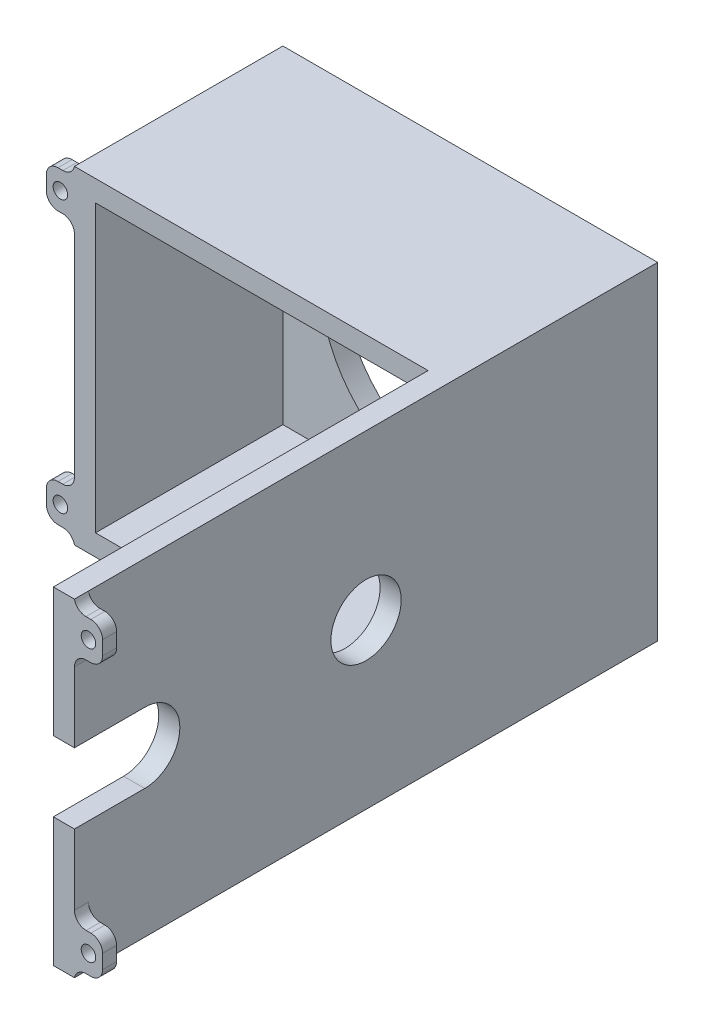
SolidWorks part; units mm, degrees
ref_plane "Front Plane" through (0, 0, 0) normal (1, 0, 0) x (0, 1, 0)
ref_plane "Top Plane" through (0, 0, 0) normal (0, 0, 1) x (0, 1, 0)
ref_plane "Right Plane" through (0, 0, 0) normal (0, 1, 0) x (-1, 0, 0)
sketch "Sketch1" plane through (0, 0, 0) normal (0, 0, 1) x (0, 1, 0)
  line L1 (-35, -40) -> (35, -40)
  line L2 (-35, -40) -> (-35, 40)
  line L3 (-35, 40) -> (35, 40)
  line L4 (35, -40) -> (35, 40)
  line L5 (-35, -40) -> (35, 40) construction
  line L6 (-35, 40) -> (35, -40) construction
  point P0 (0, 0)
  dimension "D1" = 70
  dimension "D2" = 80
extrude "Boss-Extrude1" add sketch "Sketch1" along normal blind 4.5
sketch "Sketch2" plane through (0, 0, 4.5) normal (0, 0, 1) x (1, 0, 0)
  line L0 (40, 35) -> (-40, 35) construction
  line L1 (40, -35) -> (35.5, -35)
  line L2 (40, -35) -> (40, 35)
  line L3 (40, 35) -> (35.5, 35)
  line L4 (35.5, -35) -> (35.5, 35)
  dimension "D1" = 4.5
extrude "Boss-Extrude2" add sketch "Sketch2" along normal blind 120
sketch "Sketch3" plane through (0, 0, 4.5) normal (0, 0, 1) x (1, 0, 0)
  line L0 (35.5, 35) -> (-40, 35)
  line L1 (-40, 35) -> (-40, -35)
  line L2 (-40, -35) -> (35.5, -35)
  line L3 (35.5, -35) -> (35.5, -30.5)
  line L4 (35.5, 35) -> (35.5, -35) construction
  line L5 (35.5, -30.5) -> (-35.5, -30.5)
  line L6 (-35.5, -30.5) -> (-35.5, 30.5)
  line L7 (-35.5, 30.5) -> (35.5, 30.5)
  line L8 (35.5, 30.5) -> (35.5, 35)
  dimension "D1" = 4.5
  dimension "D2" = 4.5
extrude "Boss-Extrude3" add sketch "Sketch3" along normal blind 40
sketch "Sketch4" plane through (0, 0, 0) normal (0, 0, -1) x (1, 0, 0)
  circle A0 centre (0, 0) radius 27.5
  dimension "D1" = 55
extrude "Cut-Extrude1" cut sketch "Sketch4" against normal up to next
sketch "Sketch5" plane through (35.5, 0, 0) normal (-1, 0, 0) x (0, -1, 0)
  line L0 (0, 124.5) -> (0, 0) construction
  line L1 (-35, 124.5) -> (35, 124.5) construction
  line L3 (-7.5, 124.5) -> (7.5, 124.5)
  line L4 (7.5, 124.5) -> (7.5, 109.5)
  line L5 (-7.5, 109.5) -> (-7.5, 124.5)
  line L6 (-35, 0) -> (35, 0) construction
  arc A0 (7.5, 109.5) -> (-7.5, 109.5) centre (0, 109.5) cw
  circle A1 centre (0, 62.25) radius 7.5
  dimension "D2" = 15
  dimension "D3" = 15
  dimension "D1" = 15
extrude "Cut-Extrude2" cut sketch "Sketch5" against normal up to next
sketch "Sketch6" plane through (0, 0, 124.5) normal (0, 0, 1) x (1, 0, 0)
  line L0 (35.5, 0) -> (40, 0) construction
  line L1 (35.5, 30.5) -> (35.5, -30.5) construction
  line L2 (40, -7.5) -> (40, 7.5) construction
  line L3 (40, 7.5) -> (40, 35) construction
  line L4 (40, 33) -> (46, 33)
  line L5 (40, 33) -> (40, 25)
  line L6 (40, 25) -> (46, 25)
  line L7 (46, 33) -> (46, 25)
  line L8 (40, -25) -> (46, -25)
  line L9 (46, -33) -> (46, -25)
  line L10 (40, -33) -> (46, -33)
  line L11 (40, -33) -> (40, -25)
  dimension "D1" = 25
  dimension "D2" = 8
  dimension "D3" = 6
extrude "Boss-Extrude4" add sketch "Sketch6" against normal blind 3
sketch "Sketch7" plane through (0, 0, 44.5) normal (0, 0, 1) x (1, 0, 0)
  line L0 (-40, 0) -> (-35.5, 0) construction
  line L1 (-40, 35) -> (-40, -35) construction
  line L2 (-35.5, -30.5) -> (-35.5, 30.5) construction
  line L3 (-40, -25) -> (-46, -25)
  line L4 (-40, 33) -> (-46, 33)
  line L5 (-40, 33) -> (-40, 25)
  line L6 (-40, 25) -> (-46, 25)
  line L7 (-46, 33) -> (-46, 25)
  line L8 (-46, -33) -> (-46, -25)
  line L9 (-40, -33) -> (-46, -33)
  line L10 (-40, -33) -> (-40, -25)
  dimension "D1" = 25
  dimension "D2" = 8
  dimension "D3" = 6
extrude "Boss-Extrude5" add sketch "Sketch7" against normal blind 3
sketch "Sketch8" plane through (0, 0, 44.5) normal (0, 0, 1) x (1, 0, 0)
  line L0 (-43, 33) -> (-43, 25) construction
  line L1 (-40, 33) -> (-46, 33) construction
  line L2 (-46, 25) -> (-40, 25) construction
  line L3 (-43, -25) -> (-43, -33) construction
  line L4 (-40, -25) -> (-46, -25) construction
  line L5 (-46, -33) -> (-40, -33) construction
  line L6 (43, 33) -> (43, 25) construction
  line L7 (46, 33) -> (40, 33) construction
  line L8 (40, 25) -> (46, 25) construction
  line L9 (43, -25) -> (43, -33) construction
  line L10 (46, -25) -> (40, -25) construction
  line L11 (40, -33) -> (46, -33) construction
  circle A0 centre (-43, 29) radius 1.55
  circle A1 centre (43, 29) radius 1.55
  circle A2 centre (43, -29) radius 1.55
  circle A3 centre (-43, -29) radius 1.55
  dimension "D1" = 3.1
extrude "Cut-Extrude4" cut sketch "Sketch8" against normal through all and the other way through all
fillet "Fillet1" radius 2.5 16 edges at (40, 33, 123) (46, 33, 123) (46, 25, 123) (40, 25, 123) (40, -33, 123) (40, -25, 123) (46, -25, 123) (46, -33, 123) (-40, -33, 43) (-46, -33, 43) (-46, -25, 43) (-40, -25, 43) (-40, 33, 43) (-46, 25, 43) (-40, 25, 43) (-46, 33, 43)
